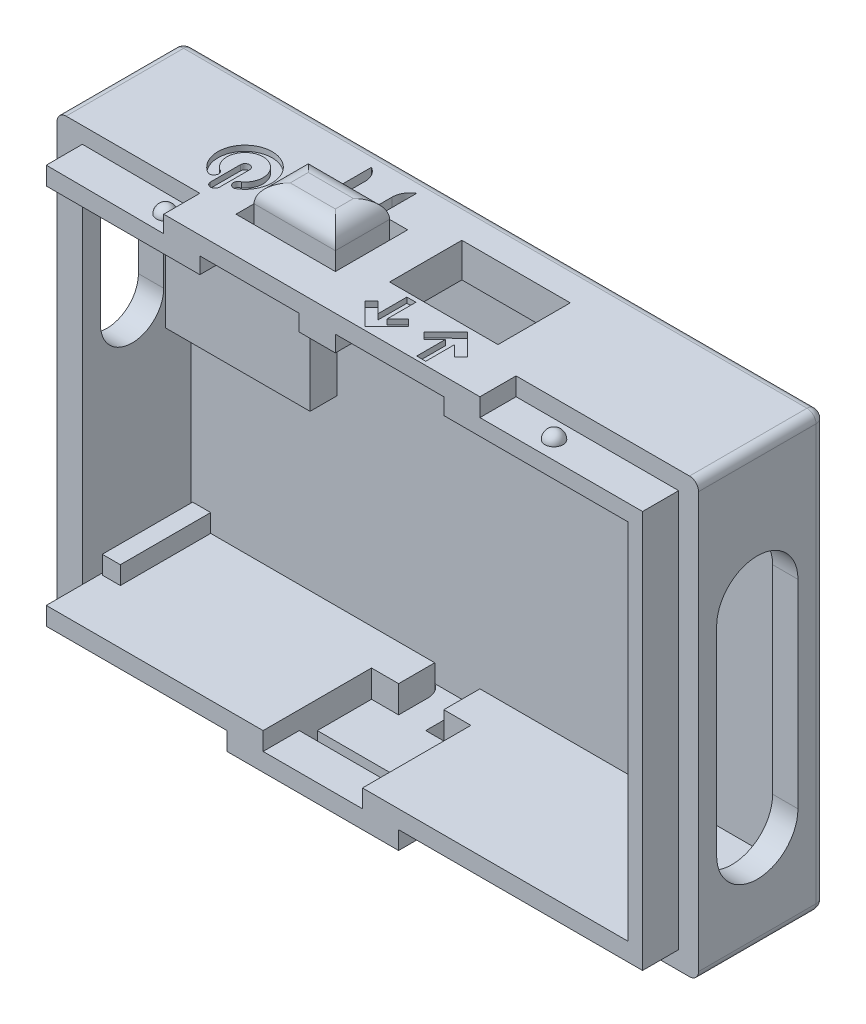
SolidWorks part; units mm, degrees
ref_plane "前视基准面" through (0, 0, 0) normal (0, 0, 1) x (1, 0, 0)
ref_plane "上视基准面" through (0, 0, 0) normal (0, 1, 0) x (1, 0, 0)
ref_plane "右视基准面" through (0, 0, 0) normal (1, 0, 0) x (0, 0, -1)
sketch "草图1" plane through (0, 0, 0) normal (0, 0, 1) x (1, 0, 0)
  line L5 (-17.75, 12) -> (17.75, 12)
  line L6 (-17.75, 12) -> (-17.75, -12)
  line L7 (-17.75, -12) -> (17.75, -12)
  line L8 (17.75, 12) -> (17.75, -12)
  line L9 (-17.75, 12) -> (17.75, -12) construction
  line L10 (-17.75, -12) -> (17.75, 12) construction
  point P0 (0, 0)
  dimension "D1" = 35.5
  dimension "D2" = 24
extrude "凸台-拉伸1" add sketch "草图1" along normal blind 7
sketch "草图2" plane through (0, 0, 7) normal (0, 0, 1) x (1, 0, 0)
  line L5 (-16.35, 11.1) -> (16.85, -11) construction
  line L6 (-16.35, -11) -> (16.85, 11.1) construction
  line L9 (-17.75, 12) -> (-17.75, -12) construction
  line L10 (-16.35, 11.1) -> (16.85, 11.1)
  line L11 (-16.35, 11.1) -> (-16.35, -11)
  line L12 (-16.35, -11) -> (16.85, -11)
  line L13 (16.85, 11.1) -> (16.85, -11)
  line L15 (17.75, 12) -> (-17.75, 12) construction
  line L16 (17.75, -12) -> (17.75, 12) construction
  point P0 (0, 0)
  dimension "D1" = 1.4
  dimension "D2" = 0.9
  dimension "D3" = 0.9
  dimension "D4" = 22.1
extrude "切除-拉伸1" cut sketch "草图2" against normal blind 6
sketch "草图3" plane through (-17.75, 0, 0) normal (-1, 0, 0) x (0, 0, 1)
  line L0 (4.25, 7.45) -> (4.25, 1.95) construction
  line L1 (6, 7.45) -> (6, 1.95)
  line L2 (2.5, 7.45) -> (2.5, 1.95)
  line L3 (0, 12) -> (0, -12) construction
  line L4 (7, 12) -> (0, 12) construction
  arc A0 (6, 7.45) -> (2.5, 7.45) centre (4.25, 7.45) ccw
  arc A1 (2.5, 1.95) -> (6, 1.95) centre (4.25, 1.95) ccw
  point P2 (4.25, 4.7)
  dimension "D3" = 5.5
  dimension "D4" = 4.55
  dimension "D1" = 2.5
  dimension "D2" = 3.5
extrude "切除-拉伸2" cut sketch "草图3" against normal blind 2
sketch "草图6" plane through (0, 0, 1) normal (0, 0, 1) x (1, 0, 0)
  line L14 (-16.35, 10.1) -> (15.85, 10.1)
  line L15 (-16.35, 11.1) -> (-16.35, -11) construction
  line L16 (15.85, 10.1) -> (15.85, -10)
  line L17 (15.85, -10) -> (-16.35, -10)
  line L18 (-16.35, -10) -> (-16.35, -11)
  line L19 (-16.35, -11) -> (16.85, -11)
  line L20 (16.85, -11) -> (16.85, 11.1)
  line L21 (16.85, 11.1) -> (-16.35, 11.1)
  line L22 (-16.35, 11.1) -> (-16.35, 10.1)
  dimension "D1" = 1
  dimension "D2" = 1
  dimension "D3" = 1
extrude "凸台-拉伸2" add sketch "草图6" along normal blind 6
sketch "草图7" plane through (0, 0, 1) normal (0, 0, 1) x (1, 0, 0)
  line L23 (15.85, 10.1) -> (10.85, 10.1)
  line L24 (15.85, 10.1) -> (15.85, 8.1)
  line L25 (15.85, 8.1) -> (10.85, 8.1)
  line L26 (10.85, 10.1) -> (10.85, 8.1)
  dimension "D3" = 5
  dimension "D8" = 2
extrude "凸台-拉伸3" add sketch "草图7" along normal blind 5
sketch "草图10" plane through (15.85, 0, 0) normal (-1, 0, 0) x (0, 0, 1)
  line L0 (3.75, -6.45) -> (3.75, 4.55) construction
  line L1 (1.5, -6.45) -> (1.5, 4.55)
  line L2 (6, -6.45) -> (6, 4.55)
  line L4 (7, -12) -> (0, -12) construction
  line L5 (7, -12) -> (7, 12) construction
  arc A0 (1.5, -6.45) -> (6, -6.45) centre (3.75, -6.45) ccw
  arc A1 (6, 4.55) -> (1.5, 4.55) centre (3.75, 4.55) ccw
  point P2 (3.75, -0.95)
  point P7 (3.75, 6.8)
  point P8 (3.75, -8.7)
  dimension "D2" = 15.5
  dimension "D1" = 4.5
  dimension "D3" = 1
  dimension "D4" = 3.3
extrude "切除-拉伸4" cut sketch "草图10" against normal blind 2
sketch "草图12" plane through (0, 0, 7) normal (0, 0, 1) x (1, 0, 0)
  line L0 (-16.35, 10.1) -> (-16.35, -10) construction
  line L8 (15.85, -10) -> (-16.35, -10) construction
  line L9 (-4.35, -10) -> (1.15, -10)
  line L10 (-4.35, -10) -> (-4.35, -12)
  line L11 (-4.35, -12) -> (1.15, -12)
  line L12 (1.15, -10) -> (1.15, -12)
  line L15 (-16.35, 10.1) -> (-16.35, -10) construction
  dimension "D1" = 12
  dimension "D2" = 17.5
  dimension "D3" = 2
extrude "切除-拉伸6" cut sketch "草图12" against normal blind 6
sketch "草图19" plane through (0, 0, 1) normal (0, 0, 1) x (1, 0, 0)
  line L0 (-16.35, 10.1) -> (10.85, 10.1) construction
  line L1 (-16.25, 10.1) -> (-8.25, 10.1)
  line L2 (-16.25, 10.1) -> (-16.25, 0.1)
  line L3 (-16.25, 0.1) -> (-8.25, 0.1)
  line L4 (-8.25, 10.1) -> (-8.25, 0.1)
  dimension "D1" = 8
  dimension "D2" = 0
  dimension "D3" = 10
extrude "USB支撑" add sketch "草图19" along normal blind 1.5
sketch "草图25" plane through (0, 0, 7) normal (0, 0, 1) x (1, 0, 0)
  line L0 (1.15, -12) -> (17.75, -12) construction
  line L2 (15.85, 8.1) -> (16.35, 8.1)
  line L3 (15.85, 8.1) -> (15.85, -10)
  line L4 (15.85, -10) -> (16.35, -10)
  line L5 (16.35, 8.1) -> (16.35, -10)
  line L7 (-16.35, 10.1) -> (15.85, 10.1) construction
  line L8 (15.85, 10.1) -> (15.85, -10) construction
  dimension "D1" = 2
  dimension "D2" = 2
  dimension "D3" = 0
  dimension "D4" = 0.5
extrude "切除-拉伸12" cut sketch "草图25" against normal blind 6
sketch "草图28" plane through (0, 0, 7) normal (0, 0, 1) x (1, 0, 0)
  line L0 (-16.35, 10.1) -> (15.85, 10.1) construction
  line L1 (-7.85, 10.1) -> (-2.35, 10.1)
  line L2 (-7.85, 10.1) -> (-7.85, 12)
  line L3 (-7.85, 12) -> (-2.35, 12)
  line L4 (-2.35, 10.1) -> (-2.35, 12)
  line L5 (17.75, 12) -> (-17.75, 12) construction
  line L6 (-16.35, 1.95) -> (-16.35, 7.45) construction
  dimension "D1" = 8.5
  dimension "D2" = 5.5
extrude "切除-拉伸13" cut sketch "草图28" against normal blind 6
sketch "草图29" plane through (0, 0, 7) normal (0, 0, 1) x (1, 0, 0)
  line L1 (-0.35, 10) -> (5.65, 10)
  line L2 (-0.35, 10) -> (-0.35, 12)
  line L3 (-0.35, 12) -> (5.65, 12)
  line L4 (5.65, 10) -> (5.65, 12)
  line L5 (17.75, 12) -> (-2.35, 12) construction
  line L8 (-16.35, 10.1) -> (-16.35, -10) construction
  dimension "D1" = 16
  dimension "D2" = 6
extrude "切除-拉伸14" cut sketch "草图29" against normal blind 5
sketch "草图34" plane through (0, 0, 1) normal (0, 0, 1) x (1, 0, 0)
  line L0 (16.35, -10) -> (1.15, -10) construction
  line L1 (-16.25, -9) -> (-15.25, -9)
  line L2 (-16.25, -9) -> (-16.25, -10)
  line L3 (-16.25, -10) -> (-15.25, -10)
  line L4 (-15.25, -9) -> (-15.25, -10)
  dimension "D1" = 1
  dimension "D2" = 1
extrude "凸台-拉伸10" add sketch "草图34" along normal blind 5
sketch "草图37" plane through (0, 0, 1) normal (0, 0, 1) x (1, 0, 0)
  line L0 (-4.35, -12) -> (1.15, -12) construction
  line L1 (-3.85, -12) -> (0.65, -12)
  line L2 (-3.85, -12) -> (-3.85, -10)
  line L3 (-3.85, -10) -> (0.65, -10)
  line L4 (0.65, -12) -> (0.65, -10)
  line L5 (1.15, -12) -> (1.15, -10) construction
  line L6 (-4.35, -10) -> (-4.35, -12) construction
  dimension "D1" = 0.5
  dimension "D2" = 0.5
  dimension "D3" = 2
extrude "凸台-拉伸12" add sketch "草图37" along normal blind 5.5
sketch "草图38" plane through (0, -12, 0) normal (0, -1, 0) x (1, 0, 0)
  line L1 (-3.85, 1) -> (-2.35, 1)
  line L2 (-3.85, 1) -> (-3.85, 3.5)
  line L3 (-3.85, 3.5) -> (-2.35, 3.5)
  line L4 (-2.35, 1) -> (-2.35, 3.5)
  line L5 (0.65, 1) -> (-0.85, 1)
  line L6 (0.65, 1) -> (0.65, 3.5)
  line L7 (0.65, 3.5) -> (-0.85, 3.5)
  line L8 (-0.85, 1) -> (-0.85, 3.5)
  dimension "D1" = 2.5
  dimension "D2" = 2.5
  dimension "D3" = 1.5
  dimension "D4" = 1.5
extrude "切除-拉伸16" cut sketch "草图38" against normal blind 2
sketch "草图39" plane through (0, 0, 6.5) normal (0, 0, 1) x (1, 0, 0)
  line L0 (0.65, -12) -> (0.65, -10) construction
  line L1 (-3.85, -10) -> (0.65, -10)
  line L2 (-3.85, -10) -> (-3.85, -11)
  line L3 (-3.85, -11) -> (0.65, -11)
  line L4 (0.65, -10) -> (0.65, -11)
  dimension "D1" = 1
extrude "切除-拉伸17" cut sketch "草图39" against normal blind 5.5
sketch "草图40" plane through (0, -12, 0) normal (0, -1, 0) x (1, 0, 0)
  line L0 (0.65, 6.5) -> (0.65, 3.5) construction
  line L1 (-3.85, 6.5) -> (0.65, 6.5)
  line L2 (-3.85, 6.5) -> (-3.85, 3.5)
  line L3 (-3.85, 3.5) -> (0.65, 3.5)
  line L4 (0.65, 6.5) -> (0.65, 3.5)
  line L6 (-3.85, 6.5) -> (0.65, 6.5) construction
  dimension "D1" = 3
  dimension "D2" = 0
  dimension "D3" = 4.5
extrude "凸台-拉伸13" add sketch "草图40" along normal blind 1.5
fillet "圆角2" radius 1 4 edges at (-1.6, -13.5, 3.5) (0.65, -13.5, 5) (-1.6, -13.5, 6.5) (-3.85, -13.5, 5)
sketch "草图41" plane through (0, 0, 1) normal (0, 0, 1) x (1, 0, 0)
  line L0 (-2.35, 12) -> (-7.85, 12) construction
  line L1 (-7.35, 12) -> (-2.85, 12)
  line L2 (-7.35, 12) -> (-7.35, 10)
  line L3 (-7.35, 10) -> (-2.85, 10)
  line L4 (-2.85, 12) -> (-2.85, 10)
  line L5 (-2.35, 10.1) -> (-2.35, 12) construction
  line L6 (-7.85, 12) -> (-7.85, 10.1) construction
  dimension "D1" = 0.5
  dimension "D2" = 0.5
  dimension "D3" = 2
extrude "凸台-拉伸14" add sketch "草图41" along normal blind 5.5
sketch "草图42" plane through (0, 12, 0) normal (0, 1, 0) x (1, 0, 0)
  line L1 (-7.35, -1) -> (-5.85, -1)
  line L2 (-7.35, -1) -> (-7.35, -3.5)
  line L3 (-7.35, -3.5) -> (-5.85, -3.5)
  line L4 (-5.85, -1) -> (-5.85, -3.5)
  line L5 (-2.85, -1) -> (-4.35, -1)
  line L6 (-2.85, -1) -> (-2.85, -3.5)
  line L7 (-2.85, -3.5) -> (-4.35, -3.5)
  line L8 (-4.35, -1) -> (-4.35, -3.5)
  dimension "D1" = 1.5
  dimension "D2" = 1.5
  dimension "D3" = 2.5
  dimension "D4" = 2.5
extrude "切除-拉伸18" cut sketch "草图42" against normal blind 2
sketch "草图43" plane through (0, 0, 6.5) normal (0, 0, 1) x (1, 0, 0)
  line L0 (-2.85, 10) -> (-2.85, 12) construction
  line L1 (-7.35, 10) -> (-2.85, 10)
  line L2 (-7.35, 10) -> (-7.35, 11)
  line L3 (-7.35, 11) -> (-2.85, 11)
  line L4 (-2.85, 10) -> (-2.85, 11)
extrude "切除-拉伸19" cut sketch "草图43" against normal blind 5.5
sketch "草图44" plane through (0, 12, 0) normal (0, 1, 0) x (1, 0, 0)
  line L0 (-2.85, -6.5) -> (-2.85, -3.5) construction
  line L1 (-7.35, -6.5) -> (-2.85, -6.5)
  line L2 (-7.35, -6.5) -> (-7.35, -3.5)
  line L3 (-7.35, -3.5) -> (-2.85, -3.5)
  line L4 (-2.85, -6.5) -> (-2.85, -3.5)
  dimension "D1" = 3
extrude "凸台-拉伸15" add sketch "草图44" along normal blind 1.5
fillet "圆角3" radius 1 4 edges at (-2.85, 13.5, 5) (-5.1, 13.5, 3.5) (-7.35, 13.5, 5) (-5.1, 13.5, 6.5)
sketch "草图45" plane through (0, 0, 7) normal (0, 0, 1) x (1, 0, 0)
  line L0 (-7.85, 10.1) -> (-16.35, 10.1)
  line L1 (-16.35, 10.1) -> (-16.35, 11.1)
  line L2 (-16.35, 11.1) -> (-7.85, 11.05)
  line L3 (-7.85, 12) -> (-7.85, 10.1) construction
  line L5 (-0.35, 12) -> (-0.35, 10.1) construction
  line L10 (-2.35, 10.1) -> (-0.35, 10.1)
  line L12 (-2.25, 11.05) -> (-0.35, 11.05)
  line L13 (-0.35, 10.1) -> (-0.35, 11.05)
  line L14 (1.25, -11) -> (-16.35, -11)
  line L16 (5.65, 10.1) -> (5.65, 11)
  line L17 (5.65, 11) -> (16.65, 11)
  line L18 (16.65, 10) -> (16.65, 11)
  line L23 (-16.35, -11) -> (-16.35, -10)
  line L24 (-16.35, -10) -> (1.15, -10)
  line L25 (-7.85, 10.1) -> (-2.35, 10.1)
  line L26 (-2.25, 11.05) -> (-7.85, 11.05)
  line L27 (16.65, 10) -> (16.65, -11)
  line L28 (16.65, -11) -> (1.25, -11)
  line L29 (1.15, -10) -> (15.85, -10)
  line L31 (16.35, -10) -> (1.15, -10) construction
  line L32 (15.85, -10) -> (15.85, 10.1)
  line L33 (15.85, 10.1) -> (5.65, 10.1)
  dimension "D1" = 1
  dimension "D4" = 1
  dimension "D5" = 11
extrude "凸台-拉伸16" add sketch "草图45" along normal blind 2
sketch "草图46" plane through (0, -11, 0) normal (0, -1, 0) x (1, 0, 0)
  line L0 (-17.75, 7) -> (-17.75, 0) construction
  line L2 (-11.25, 8) -> (-10.25, 8)
  line L4 (-16.35, 7) -> (-4.35, 7) construction
  arc A3 (-11.25, 8) -> (-10.25, 8) centre (-10.75, 8) cw
  dimension "D1" = 1
  dimension "D2" = 7
  dimension "D4" = 0.5
  dimension "D3" = 1
revolve "旋转1" add sketch "草图46" angle 360 about L2
sketch "草图47" plane through (0, -11, 0) normal (0, -1, 0) x (1, 0, 0)
  line L0 (11.25, 8) -> (10.25, 8)
  line L1 (1.15, 7) -> (17.75, 7) construction
  line L3 (17.75, 7) -> (17.75, 0) construction
  arc A0 (10.25, 8) -> (11.25, 8) centre (10.75, 8) cw
  dimension "D2" = 0.5
  dimension "D1" = 1
  dimension "D3" = 1
  dimension "D4" = 7
revolve "旋转2" add sketch "草图47" angle 360 about L0
sketch "草图48" plane through (0, 11.05, 0) normal (0, 1, 0) x (1, 0, 0)
  line L0 (-11.25, -8) -> (-10.25, -8)
  line L2 (-0.35, -9) -> (-7.85, -9) construction
  line L3 (-17.75, -7) -> (-17.75, 0) construction
  arc A0 (-11.25, -8) -> (-10.25, -8) centre (-10.75, -8) cw
  dimension "D2" = 0.5
  dimension "D1" = 1
  dimension "D3" = 7
  dimension "D4" = 1
revolve "旋转3" add sketch "草图48" angle 360 about L0
sketch "草图49" plane through (0, 11, 0) normal (0, 1, 0) x (1, 0, 0)
  line L0 (10.25, -8) -> (11.25, -8)
  line L1 (16.65, -9) -> (5.65, -9) construction
  line L3 (17.75, -7) -> (17.75, 0) construction
  arc A0 (10.25, -8) -> (11.25, -8) centre (10.75, -8) cw
  dimension "D2" = 0.5
  dimension "D1" = 1
  dimension "D3" = 1
  dimension "D4" = 7
revolve "旋转4" add sketch "草图49" angle 360 about L0
sketch "草图50" plane through (0, 10.1, 0) normal (0, -1, 0) x (1, 0, 0)
  line L0 (-16.35, 9) -> (-0.35, 9) construction
  line L1 (-7.85, 7) -> (-2.35, 7)
  line L2 (-7.85, 7) -> (-7.85, 9)
  line L3 (-7.85, 9) -> (-2.35, 9)
  line L4 (-2.35, 7) -> (-2.35, 9)
extrude "切除-拉伸20" cut sketch "草图50" against normal blind 2
sketch "草图51" plane through (0, -11, 0) normal (0, -1, 0) x (1, 0, 0)
  line L0 (-16.35, 9) -> (16.65, 9) construction
  line L1 (-4.35, 7) -> (1.15, 7)
  line L2 (-4.35, 7) -> (-4.35, 9)
  line L3 (-4.35, 9) -> (1.15, 9)
  line L4 (1.15, 7) -> (1.15, 9)
extrude "切除-拉伸21" cut sketch "草图51" against normal blind 2
sketch "草图54" plane through (0, 0, 7) normal (0, 0, 1) x (1, 0, 0)
  line L1 (-7.85, 11.05) -> (-9.85, 11.05)
  line L2 (-7.85, 11.05) -> (-7.85, 12)
  line L3 (-7.85, 12) -> (-9.85, 12)
  line L4 (-9.85, 11.05) -> (-9.85, 12)
  dimension "D1" = 2
extrude "凸台-拉伸19" add sketch "草图54" along normal blind 2
sketch "草图55" plane through (-7.85, 0, 0) normal (1, 0, 0) x (0, 0, -1)
  line L5 (-9, 12) -> (-7, 12)
  line L6 (-9, 12) -> (-9, 11)
  line L7 (-9, 11) -> (-7, 11)
  line L8 (-7, 12) -> (-7, 11)
  dimension "D1" = 1
  dimension "D2" = 2
extrude "凸台-拉伸20" add sketch "草图55" along normal blind 15.5
sketch "草图56" plane through (0, 0, 7) normal (0, 0, 1) x (1, 0, 0)
  line L0 (-16.35, -11) -> (-4.35, -11) construction
  line L1 (-4.35, -12) -> (-6.35, -12)
  line L2 (-4.35, -12) -> (-4.35, -11)
  line L3 (-4.35, -11) -> (-6.35, -11)
  line L4 (-6.35, -12) -> (-6.35, -11)
  dimension "D1" = 2
extrude "凸台-拉伸21" add sketch "草图56" along normal blind 2
sketch "草图57" plane through (-4.35, 0, 0) normal (1, 0, 0) x (0, 0, -1)
  line L1 (-9, -12) -> (-7, -12)
  line L2 (-9, -12) -> (-9, -11)
  line L3 (-9, -11) -> (-7, -11)
  line L4 (-7, -12) -> (-7, -11)
  dimension "D1" = 1
  dimension "D2" = 2
extrude "凸台-拉伸22" add sketch "草图57" along normal blind 7.5
sketch "草图58" plane through (0, 0, 1) normal (0, 0, 1) x (1, 0, 0)
  line L0 (-0.85, -12) -> (1.15, -12) construction
  line L1 (-7.85, 12) -> (-6.35, 12)
  line L2 (-7.85, 12) -> (-7.85, 10.1)
  line L3 (-7.85, 10.1) -> (-6.35, 10.1)
  line L4 (-6.35, 12) -> (-6.35, 10.1)
  line L5 (-2.35, 12) -> (-3.85, 12)
  line L6 (-2.35, 12) -> (-2.35, 10.1)
  line L7 (-2.35, 10.1) -> (-3.85, 10.1)
  line L8 (-3.85, 12) -> (-3.85, 10.1)
  line L9 (-4.35, -12) -> (-2.85, -12)
  line L10 (-4.35, -12) -> (-4.35, -10)
  line L11 (-4.35, -10) -> (-2.85, -10)
  line L12 (-2.85, -12) -> (-2.85, -10)
  line L13 (1.15, -10) -> (-0.35, -10)
  line L14 (1.15, -10) -> (1.15, -12)
  line L15 (1.15, -12) -> (-0.35, -12)
  line L16 (-0.35, -10) -> (-0.35, -12)
  dimension "D1" = 1.5
  dimension "D2" = 1.5
  dimension "D3" = 1.9
  dimension "D4" = 1.9
  dimension "D5" = 2
  dimension "D6" = 1.5
  dimension "D7" = 1.5
extrude "凸台-拉伸24" add sketch "草图58" along normal blind 2
sketch "草图59" plane through (0, 0, 7) normal (0, 0, -1) x (-1, 0, 0)
  line L1 (-5.65, 12) -> (0.35, 12)
  line L2 (-5.65, 12) -> (-5.65, 11)
  line L3 (-5.65, 11) -> (0.35, 11)
  line L4 (0.35, 12) -> (0.35, 11)
extrude "凸台-拉伸25" add sketch "草图59" along normal blind 1
sketch "草图60" plane through (0, 12, 0) normal (0, 1, 0) x (1, 0, 0)
  line L0 (4.45, -8.8) -> (4.45, -7.2)
  line L1 (4.45, -7.2) -> (5.0493, -7.8)
  line L2 (5.0493, -7.8) -> (5.4031, -7.4466)
  line L3 (5.4031, -7.4466) -> (4.2007, -6.2429)
  line L4 (4.2007, -6.2429) -> (2.996, -7.4463)
  line L5 (2.996, -7.4463) -> (3.3493, -7.8)
  line L6 (3.3493, -7.8) -> (3.95, -7.2)
  line L7 (3.95, -7.2) -> (3.95, -8.8)
  line L8 (3.95, -8.8) -> (4.45, -8.8)
  line L9 (1.35, -6.2429) -> (0.85, -6.2429)
  line L10 (0.85, -6.2429) -> (0.85, -7.8429)
  line L11 (0.85, -7.8429) -> (0.2507, -7.2429)
  line L12 (0.2507, -7.2429) -> (-0.1031, -7.5963)
  line L13 (-0.1031, -7.5963) -> (1.0993, -8.8)
  line L14 (1.0993, -8.8) -> (2.304, -7.5966)
  line L15 (2.304, -7.5966) -> (1.9507, -7.2429)
  line L16 (1.9507, -7.2429) -> (1.35, -7.8429)
  line L17 (1.35, -7.8429) -> (1.35, -6.2429)
  line L18 (7.65, -9) -> (-9.85, -9) construction
  line L19 (5.65, -2) -> (5.65, -6) construction
  line L20 (-0.35, -2) -> (-0.35, -6) construction
  point P9 (4.2, -8.8)
  dimension "D1" = 0.5
  dimension "D2" = 0.5
  dimension "D3" = 0.5
  dimension "D4" = 1.6
  dimension "D5" = 1.6
  dimension "D6" = 1
  dimension "D7" = 1
  dimension "D8" = 0.5
  dimension "D9" = 0.5
  dimension "D10" = 0.5
  dimension "D11" = 1
  dimension "D12" = 1
  dimension "D13" = 1.6
  dimension "D14" = 1.6
  dimension "D15" = 0.2
  dimension "D16" = 0.2
  dimension "D17" = 1.2
  dimension "D18" = 1.2
sketch "草图61" plane through (0, 12, 0) normal (0, 1, 0) x (1, 0, 0)
  line L1 (-7.85, -3) -> (-7.85, -7) construction
  line L2 (17.75, 0) -> (-17.75, 0) construction
  line L3 (-9.6, -6.1596) -> (-9.6, -4.5)
  line L4 (-10.1, -6.1596) -> (-10.1, -4.5)
  arc A0 (-9.1017, -5.8) -> (-10.5983, -5.8) centre (-9.85, -4.5) ccw
  arc A1 (-9.25, -5.3) -> (-10.45, -5.3) centre (-9.85, -4.5) ccw
  arc A4 (-9.6, -6.1596) -> (-10.1, -6.1596) centre (-9.85, -6.1596) cw
  arc A5 (-9.6, -4.5) -> (-10.1, -4.5) centre (-9.85, -4.5) ccw
  arc A8 (-9.1017, -5.8) -> (-9.25, -5.3) centre (-9.1758, -5.55) cw
  arc A9 (-10.5983, -5.8) -> (-10.45, -5.3) centre (-10.5242, -5.55) ccw
  dimension "D1" = 1.5
  dimension "D2" = 1
  dimension "D7" = 5.3
  dimension "D3" = 4.5
  dimension "D4" = 4.5
  dimension "D5" = 2
  dimension "D6" = 2
  dimension "D8" = 5.3
  dimension "D9" = 5.8
  dimension "D10" = 5.8
  dimension "D11" = 0.5
extrude "切除-拉伸22" cut sketch "草图61" against normal blind 0.3
extrude "切除-拉伸23" cut sketch "草图60" against normal blind 0.3
fillet "圆角4" radius 0.5 8 edges at (0, -12, 0) (17.75, 0, 0) (0, 12, 0) (-17.75, 0, 0) (-17.75, 12, 3.5) (-17.75, -12, 3.5) (17.75, -12, 3.5) (17.75, 12, 3.5)
fillet "圆角5" radius 1 4 edges at (-2.35, -11.5, 1) (-0.85, -11.5, 1) (-5.85, 11.5, 1) (-4.35, 11.5, 1)
